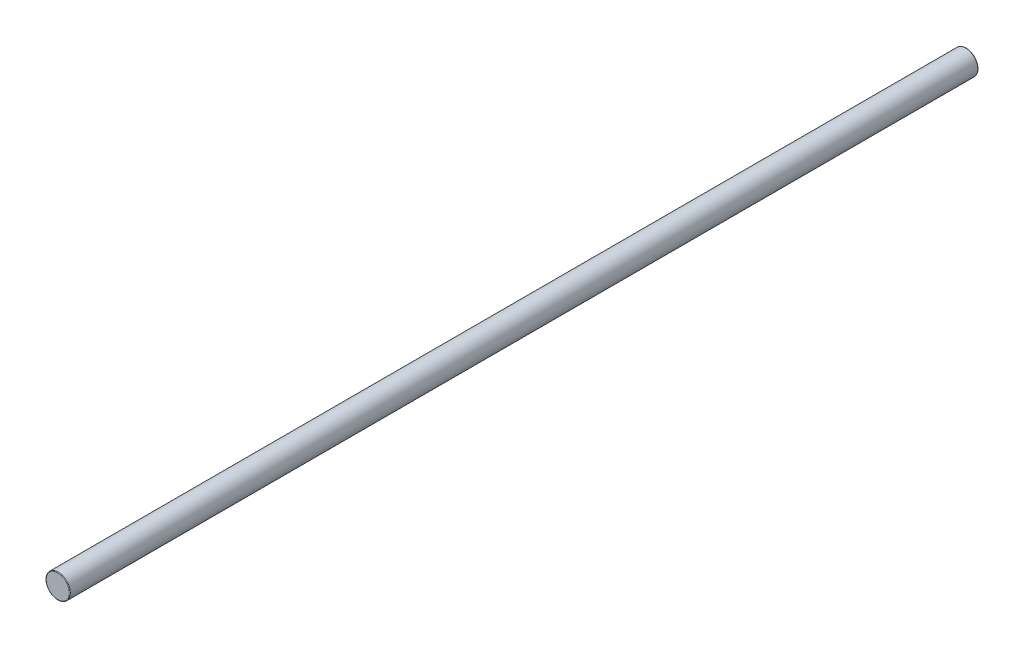
SolidWorks part; units mm, degrees
material "AISI 304"
ref_plane "Front Plane" through (0, 0, 0) normal (0, 0, 1) x (1, 0, 0)
ref_plane "Top Plane" through (0, 0, 0) normal (0, 1, 0) x (1, 0, 0)
ref_plane "Right Plane" through (0, 0, 0) normal (1, 0, 0) x (0, 0, -1)
sketch "Sketch1" plane through (0, 0, 0) normal (0, 0, 1) x (1, 0, 0)
  circle A0 centre (0, 0) radius 4
  dimension "D1" = 8
extrude "Boss-Extrude1" add sketch "Sketch1" against normal blind 300
fillet "Fillet1" radius 0.2 2 edges at (4, 0, -300) (4, 0, 0)
sketch "Sketch2" plane through (0, 0, 0) normal (0, 0, 1) x (1, 0, 0)
  circle A0 centre (0, 0) radius 4
  dimension "D1" = 8
sketch "Sketch3" plane through (0, 0, 0) normal (0, 1, 0) x (1, 0, 0)
  line L0 (3, 0.35) -> (3, 0.05)
  line L1 (3, 0.05) -> (5, -0.75)
  line L2 (5, -0.75) -> (5, 1.15)
  line L3 (5, 1.15) -> (3, 0.35)
  line L4 (5, 0.2) -> (3, 0.2)
  line L7 (4, 0.2) -> (-4, 0.2) construction
  point P7 (4, 0.2)
  dimension "D1" = 1.9
  dimension "D2" = 2
  dimension "D3" = 0.3
  dimension "D4" = 4
curve "Helix/Spiral1" [suppressed] pitch 2 height 400 turns 200
sweep "Cut-Sweep1" [suppressed] cut profiles "Sketch3" path "Helix/Spiral1"
